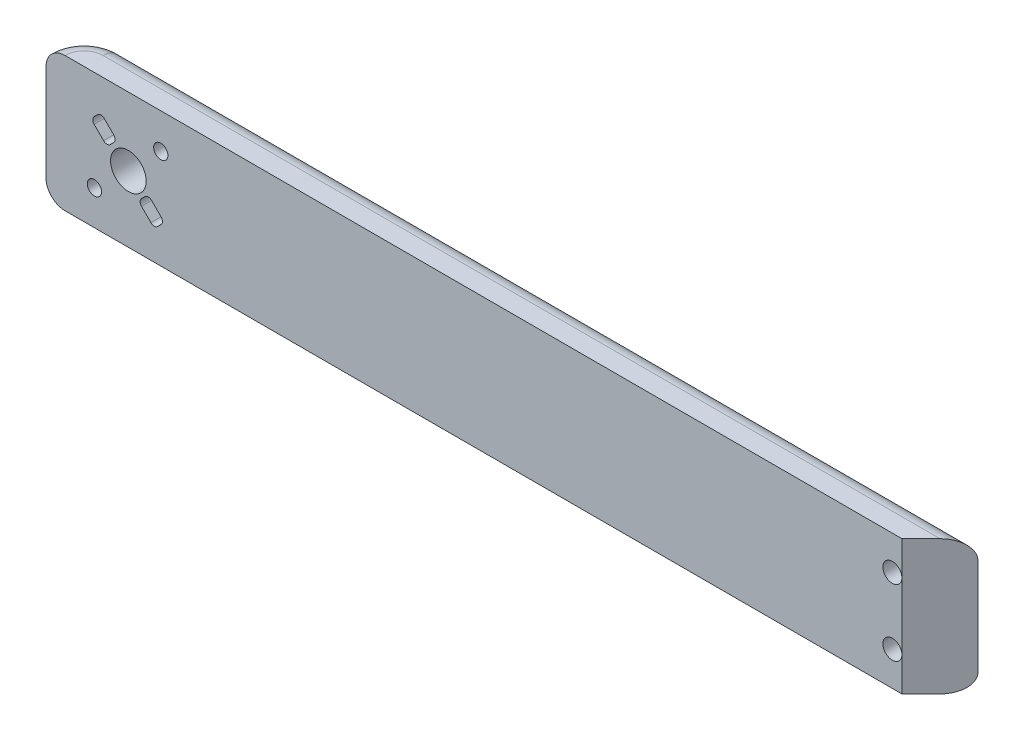
SolidWorks part; units mm, degrees
ref_plane "Plan de face" through (0, 0, 0) normal (0, 0, 1) x (1, 0, 0)
ref_plane "Plan de dessus" through (0, 0, 0) normal (0, 1, 0) x (1, 0, 0)
ref_plane "Plan de droite" through (0, 0, 0) normal (1, 0, 0) x (0, 0, -1)
sketch "Esquisse1" plane through (0, 0, 0) normal (0, 0, 1) x (1, 0, 0)
  line L1 (0, 0) -> (200, 0)
  line L2 (0, 0) -> (0, 28.284)
  line L3 (0, 28.284) -> (200, 28.284)
  line L4 (200, 0) -> (200, 28.284)
  dimension "D1" = 200
  dimension "D2" = 28.284
extrude "Boss.-Extru.3" add sketch "Esquisse1" along normal blind 8
chamfer "Chanfrein1" distance 20 angle 45 1 edges at (200, 14.142, 8)
sketch "Esquisse4" plane through (0, 0, 8) normal (0, 0, 1) x (1, 0, 0)
  line L0 (0, 0) -> (180, 0) construction
  line L2 (180, 0) -> (180, 28.284) construction
  line L5 (180, 28.284) -> (0, 28.284) construction
  circle A0 centre (178, 7.142) radius 2
  circle A1 centre (178, 21.142) radius 2
  dimension "D3" = 4
  dimension "D4" = 4
  dimension "D1" = 7.142
  dimension "D2" = 7.142
  dimension "D5" = 2
  dimension "D6" = 2
extrude "Enlèv. mat.-Extru.1" cut sketch "Esquisse4" against normal blind 8
fillet "Fillet1" radius 8 1 edges at (0, 14.142, 0)
sketch "Sketch2" plane through (0, 0, 8) normal (0, 0, 1) x (1, 0, 0)
  line L4 (14.9435, 18.2434) -> (12.8222, 16.122)
  line L6 (19.3798, 9.5645) -> (22.78, 6.1646)
  line L9 (12.8222, 16.122) -> (9.4222, 19.522)
  line L11 (11.5435, 21.6434) -> (14.9435, 18.2434)
  line L16 (22.78, 6.1646) -> (24.9012, 8.286)
  line L24 (9.4222, 19.522) -> (11.5435, 21.6434)
  line L26 (24.9012, 8.286) -> (21.5011, 11.6858)
  line L27 (21.5011, 11.6858) -> (19.3798, 9.5645)
  circle A0 centre (10.1805, 7.2815) radius 1.5
  circle A3 centre (24.1429, 20.8833) radius 1.5
  circle A4 centre (17.323, 13.9183) radius 3.75
  dimension "D4" = 3
  dimension "D6" = 3
  dimension "D3" = 7.5
  dimension "D1" = 9.75
  dimension "D9" = 19.4925
extrude "Cut-Extrude1" cut sketch "Sketch2" against normal blind 8
fillet "Fillet9" radius 1 4 edges at (9.4222, 19.522, 4) (11.5435, 21.6434, 4) (12.8222, 16.122, 4) (14.9435, 18.2434, 4)
fillet "Fillet10" radius 1 4 edges at (24.9012, 8.286, 4) (22.78, 6.1646, 4) (21.5011, 11.6858, 4) (19.3798, 9.5645, 4)
sketch "Sketch3" plane through (0, 0, 8) normal (0, 0, 1) x (1, 0, 0)
  circle A0 centre (17.5366, 14.6901) radius 2.1502
fillet "Fillet4" radius 4 2 edges at (98, 0, 0) (2.3431, 0, 2.3431)
fillet "Fillet5" radius 4 2 edges at (98, 28.284, 0) (2.3431, 28.284, 2.3431)
